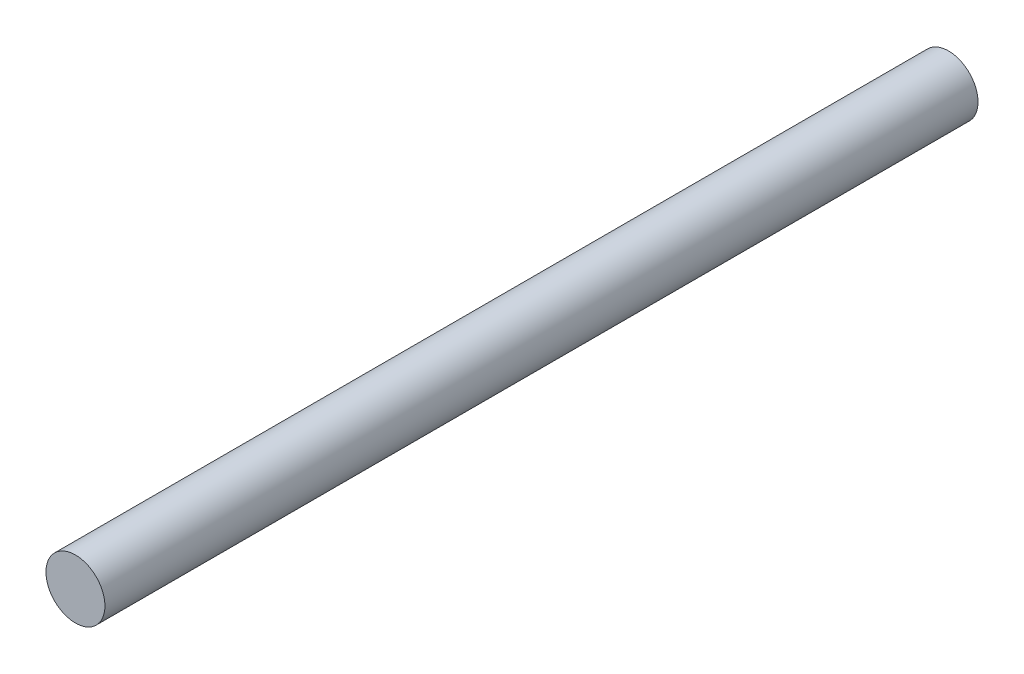
SolidWorks part; units mm, degrees
material "AISI 1020 Steel, Cold Rolled"
ref_plane "Front Plane" through (0, 0, 0) normal (0, 0, 1) x (1, 0, 0)
ref_plane "Top Plane" through (0, 0, 0) normal (0, 1, 0) x (1, 0, 0)
ref_plane "Right Plane" through (0, 0, 0) normal (1, 0, 0) x (0, 0, -1)
sketch "Sketch2" plane through (0, 0, 0) normal (0, 0, 1) x (1, 0, 0)
  circle A0 centre (0, 0) radius 6.35
  dimension "D1" = 12.7
extrude "Boss-Extrude1" add sketch "Sketch2" along normal blind 187.96
sketch "Sketch3" [suppressed] plane through (0, 0, 220.98) normal (0, 0, 1) x (1, 0, 0)
  circle A0 centre (0, 0) radius 6.35
extrude "Cut-Extrude1" [suppressed] cut sketch "Sketch3" against normal blind 26.416
sketch "Sketch4" [suppressed] plane through (0, 0, 194.564) normal (0, 0, 1) x (1, 0, 0)
  circle A0 centre (0, 0) radius 3.175
  dimension "D1" = 6.35
extrude "Boss-Extrude2" [suppressed] add sketch "Sketch4" along normal blind 26.416
sketch "Sketch5" [suppressed] plane through (0, 0, 0) normal (0, 0, -1) x (-1, 0, 0)
  circle A0 centre (0, 0) radius 6.35
extrude "Cut-Extrude2" [suppressed] cut sketch "Sketch5" against normal blind 26.416
sketch "Sketch6" [suppressed] plane through (0, 0, 26.416) normal (0, 0, -1) x (-1, 0, 0)
  circle A0 centre (0, 0) radius 3.175
  dimension "D1" = 6.35
extrude "Boss-Extrude3" [suppressed] add sketch "Sketch6" along normal blind 26.416
sketch "Sketch7" [suppressed] plane through (0, 0, 0) normal (0, 0, -1) x (-1, 0, 0)
  circle A0 centre (0, 0) radius 14.231
extrude "Cut-Extrude3" [suppressed] cut sketch "Sketch7" against normal blind 27.432
sketch "Sketch8" [suppressed] plane through (0, 0, 27.432) normal (0, 0, -1) x (-1, 0, 0)
  circle A0 centre (0, 0) radius 3.175
  dimension "D1" = 6.35
extrude "Boss-Extrude4" [suppressed] add sketch "Sketch8" along normal blind 27.432
sketch "Sketch9" [suppressed] plane through (0, 0, 220.98) normal (0, 0, 1) x (1, 0, 0)
  circle A0 centre (0, 0) radius 8.8374
extrude "Cut-Extrude4" [suppressed] cut sketch "Sketch9" against normal blind 27.432
sketch "Sketch10" [suppressed] plane through (0, 0, 193.548) normal (0, 0, 1) x (1, 0, 0)
  circle A0 centre (0, 0) radius 3.175
  dimension "D1" = 6.35
extrude "Boss-Extrude5" [suppressed] add sketch "Sketch10" along normal blind 27.432
